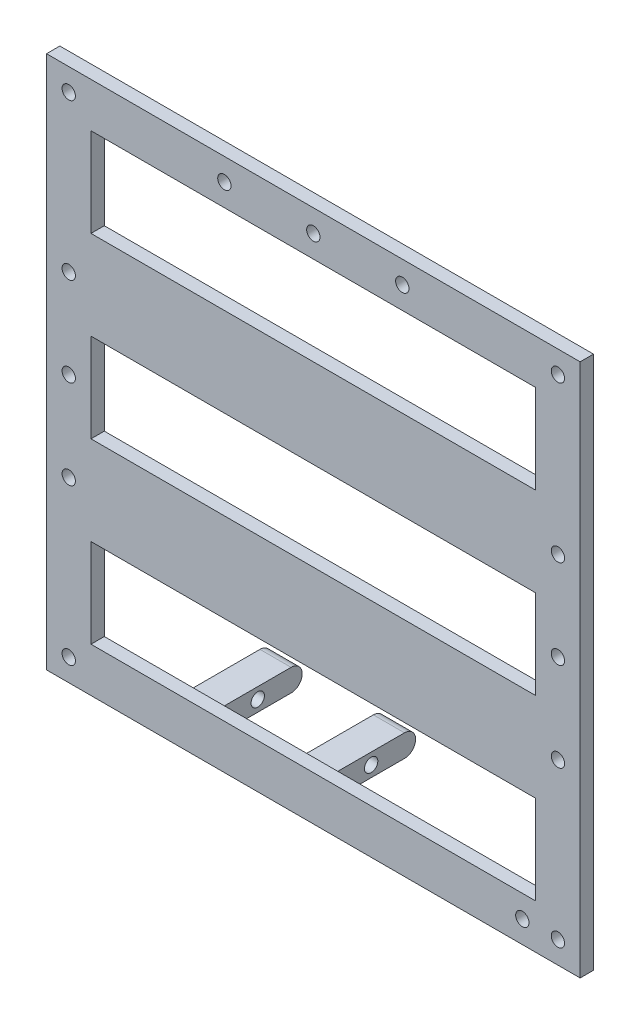
SolidWorks part; units mm, degrees
ref_plane "Plano frontal" through (0, 0, 0) normal (0, 0, 1) x (1, 0, 0)
ref_plane "Plano superior" through (0, 0, 0) normal (0, 1, 0) x (1, 0, 0)
ref_plane "Plano direito" through (0, 0, 0) normal (1, 0, 0) x (0, 0, -1)
sketch "Esboço1" plane through (0, 0, 0) normal (0, 0, 1) x (1, 0, 0)
  line L1 (-6.5269, 6.3462) -> (113.4731, 6.3462)
  line L2 (-6.5269, 6.3462) -> (-6.5269, -113.6538)
  line L3 (-6.5269, -113.6538) -> (113.4731, -113.6538)
  line L4 (113.4731, 6.3462) -> (113.4731, -113.6538)
  dimension "D1" = 120
  dimension "D2" = 120
extrude "Ressalto-extrusão1" add sketch "Esboço1" along normal blind 3
sketch "Esboço2" plane through (0, 0, 3) normal (0, 0, 1) x (1, 0, 0)
  line L0 (-6.5269, 6.3462) -> (-6.5269, -113.6538) construction
  line L1 (3.4731, -103.6538) -> (103.4731, -103.6538)
  line L2 (3.4731, -103.6538) -> (3.4731, -3.6538)
  line L3 (3.4731, -3.6538) -> (103.4731, -3.6538)
  line L4 (103.4731, -103.6538) -> (103.4731, -3.6538)
  line L5 (113.4731, 6.3462) -> (-6.5269, 6.3462) construction
  line L6 (113.4731, -113.6538) -> (113.4731, 6.3462) construction
  line L7 (-6.5269, -113.6538) -> (113.4731, -113.6538) construction
  dimension "D1" = 10
  dimension "D2" = 10
  dimension "D3" = 10
  dimension "D4" = 10
extrude "Corte-extrusão1" cut sketch "Esboço2" against normal through all
sketch "Esboço5" plane through (0, 0, 0) normal (0, 0, -1) x (-1, 0, 0)
  line L0 (-3.4731, -103.6538) -> (-103.4731, -103.6538) construction
  line L1 (-53.4731, -111.1538) -> (-46.4731, -111.1538)
  line L2 (-53.4731, -111.1538) -> (-53.4731, -106.1538)
  line L3 (-53.4731, -106.1538) -> (-46.4731, -106.1538)
  line L4 (-46.4731, -111.1538) -> (-46.4731, -106.1538)
  line L5 (-113.4731, -113.6538) -> (-113.4731, 6.3462) construction
  line L6 (-27.9731, -111.1538) -> (-20.9731, -111.1538)
  line L7 (-27.9731, -111.1538) -> (-27.9731, -106.1538)
  line L8 (-27.9731, -106.1538) -> (-20.9731, -106.1538)
  line L9 (-20.9731, -111.1538) -> (-20.9731, -106.1538)
  dimension "D1" = 5
  dimension "D2" = 2.5
  dimension "D3" = 7
  dimension "D4" = 5
  dimension "D5" = 2.5
  dimension "D6" = 18.5
  dimension "D7" = 60
  dimension "D8" = 7
extrude "Ressalto-extrusão2" add sketch "Esboço5" along normal blind 20
sketch "Esboço6" plane through (0, 0, 0) normal (0, 0, -1) x (-1, 0, 0)
  line L0 (-113.4731, 6.3462) -> (6.5269, 6.3462) construction
  line L1 (6.5269, 6.3462) -> (6.5269, -113.6538) construction
  line L2 (6.5269, -113.6538) -> (-113.4731, -113.6538) construction
  line L3 (-53.4731, 6.3462) -> (-53.4731, -41.3849) construction
  circle A0 centre (1.5269, -108.6538) radius 1.5
  circle A1 centre (1.5269, -73.6538) radius 1.5
  circle A2 centre (1.5269, -53.6538) radius 1.5
  circle A3 centre (1.5269, -33.6538) radius 1.5
  circle A4 centre (1.5269, 1.3462) radius 1.5
  circle A5 centre (-108.4731, 1.3462) radius 1.5
  circle A6 centre (-108.4731, -33.6538) radius 1.5
  circle A7 centre (-108.4731, -53.6538) radius 1.5
  circle A8 centre (-108.4731, -73.6538) radius 1.5
  circle A9 centre (-108.4731, -108.6538) radius 1.5
  dimension "D1" = 5
  dimension "D2" = 5
  dimension "D3" = 35
  dimension "D4" = 5
  dimension "D5" = 5
  dimension "D6" = 35
  dimension "D7" = 3
  dimension "D8" = 5
  dimension "D9" = 20
  dimension "D10" = 3
  dimension "D11" = 5
  dimension "D12" = 5
  dimension "D13" = 3
  dimension "D14" = 3
  dimension "D15" = 3
extrude "Corte-extrusão2" cut sketch "Esboço6" against normal blind 10
sketch "Esboço7" plane through (0, 0, 0) normal (0, 0, -1) x (-1, 0, 0)
  line L0 (6.5269, -113.6538) -> (-113.4731, -113.6538) construction
  circle A0 centre (-100.4731, -108.6538) radius 1.5
  circle A1 centre (-108.4731, -108.6538) radius 1.5 construction
  dimension "D1" = 3
  dimension "D2" = 8
  dimension "D3" = 5
extrude "Corte-extrusão3" cut sketch "Esboço7" against normal through all
sketch "Esboço8" plane through (20.9731, 0, 0) normal (-1, 0, 0) x (0, 0, 1)
  line L0 (-20, -106.1538) -> (0, -106.1538) construction
  line L1 (-20, -111.1538) -> (-20, -106.1538) construction
  circle A0 centre (-10, -108.6538) radius 1.5
  dimension "D1" = 3
  dimension "D2" = 2.5
  dimension "D3" = 10
extrude "Corte-extrusão4" cut sketch "Esboço8" against normal through all
fillet "Filete2" radius 2.5 12 edges at (49.9731, -106.1538, 0) (49.9731, -106.1538, -20) (49.9731, -111.1538, -20) (46.4731, -108.6538, 0) (53.4731, -108.6538, 0) (49.9731, -111.1538, 0) (24.4731, -106.1538, -20) (24.4731, -111.1538, -20) (24.4731, -106.1538, 0) (27.9731, -108.6538, 0) (24.4731, -111.1538, 0) (20.9731, -108.6538, 0)
sketch "Esboço9" plane through (0, 0, 0) normal (0, 0, -1) x (-1, 0, 0)
  line L0 (-3.4731, -3.6538) -> (-3.4731, -103.6538) construction
  line L1 (-3.4731, -83.6538) -> (-103.4731, -83.6538)
  line L2 (-3.4731, -83.6538) -> (-3.4731, -63.6538)
  line L3 (-3.4731, -63.6538) -> (-103.4731, -63.6538)
  line L4 (-103.4731, -83.6538) -> (-103.4731, -63.6538)
  line L5 (-103.4731, -103.6538) -> (-103.4731, -3.6538) construction
  line L6 (-3.4731, -103.6538) -> (-18.4731, -103.6538) construction
  line L7 (-3.4731, -43.6538) -> (-103.4731, -43.6538)
  line L8 (-3.4731, -43.6538) -> (-3.4731, -23.6538)
  line L9 (-3.4731, -23.6538) -> (-103.4731, -23.6538)
  line L10 (-103.4731, -43.6538) -> (-103.4731, -23.6538)
  dimension "D1" = 20
  dimension "D2" = 20
  dimension "D3" = 20
  dimension "D4" = 20
extrude "Ressalto-extrusão3" add sketch "Esboço9" against normal blind 3
sketch "Esboço10" plane through (0, 0, 0) normal (0, 0, -1) x (-1, 0, 0)
  line L0 (-113.4731, 6.3462) -> (6.5269, 6.3462) construction
  circle A0 centre (-33.4731, 1.3462) radius 1.5
  circle A1 centre (-53.4731, 1.3462) radius 1.5
  circle A2 centre (-73.4731, 1.3462) radius 1.5
  circle A3 centre (1.5269, 1.3462) radius 1.5 construction
  circle A5 centre (-108.4731, 1.3462) radius 1.5 construction
  dimension "D1" = 3
  dimension "D2" = 3
  dimension "D3" = 3
  dimension "D4" = 5
  dimension "D5" = 5
  dimension "D6" = 5
  dimension "D7" = 35
  dimension "D8" = 35
  dimension "D9" = 20
extrude "Corte-extrusão5" cut sketch "Esboço10" against normal blind 10
